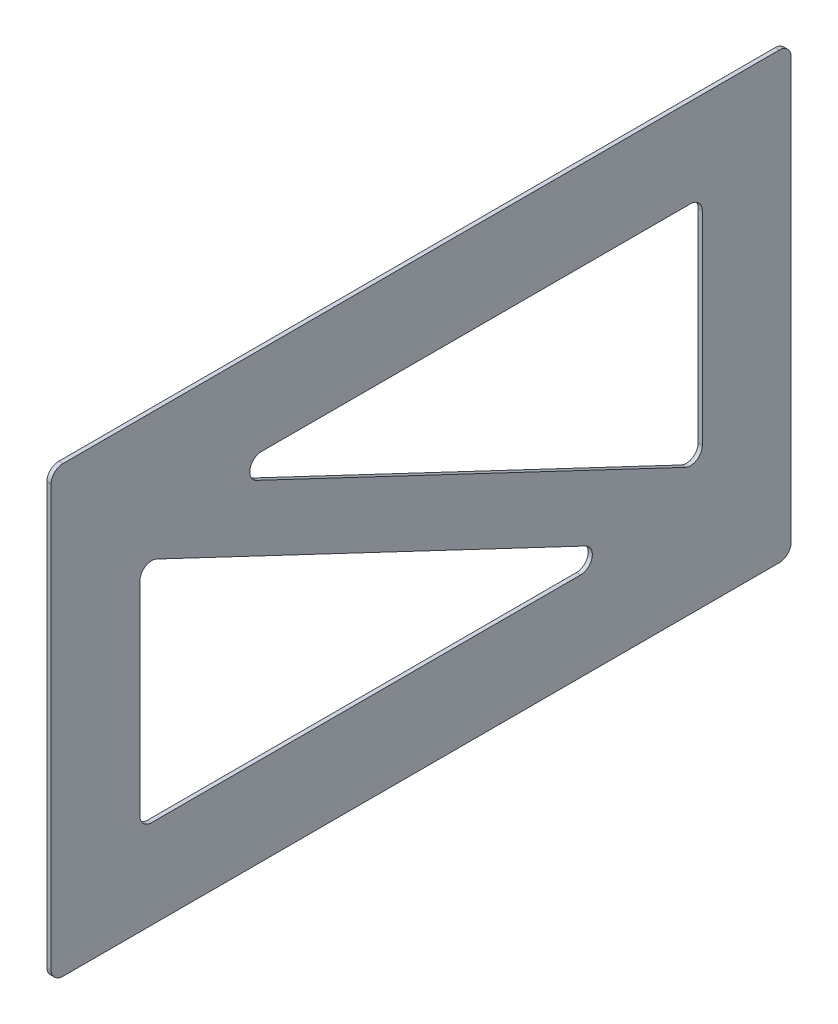
SolidWorks part; units mm, degrees
ref_plane "Front Plane" through (0, 0, 0) normal (0, 0, 1) x (1, 0, 0)
ref_plane "Top Plane" through (0, 0, 0) normal (0, 1, 0) x (1, 0, 0)
ref_plane "Right Plane" through (0, 0, 0) normal (1, 0, 0) x (0, 0, -1)
sketch "Sketch1" plane through (0, 0, 0) normal (1, 0, 0) x (0, 0, -1)
  line L1 (-62.5, 37.5) -> (62.5, 37.5)
  line L2 (-62.5, 37.5) -> (-62.5, -37.5)
  line L3 (-62.5, -37.5) -> (62.5, -37.5)
  line L4 (62.5, 37.5) -> (62.5, -37.5)
  line L5 (-62.5, 37.5) -> (62.5, -37.5) construction
  line L6 (-62.5, -37.5) -> (62.5, 37.5) construction
  point P0 (0, 0)
  dimension "D1" = 125
  dimension "D2" = 75
sheet metal parameters "Sheet-Metal1" thickness 0.7 parameters "D1"=0.7366
base flange "Base-Flange1" sketch "Sketch1" thickness 0.7 reverse thickness direction no parameters "D1"=0.7366
sketch "Sketch10" plane through (0, 0, 0) normal (1, 0, 0) x (0, 0, -1)
  line L0 (-47.5, 22.5) -> (-47.5, -22.5)
  line L1 (-47.5, -22.5) -> (47.5, -22.5)
  line L2 (47.5, -22.5) -> (47.5, 22.5)
  line L3 (47.5, 22.5) -> (-47.5, 22.5)
  line L4 (62.5, 37.5) -> (-62.5, 37.5) construction
  line L5 (-62.5, -37.5) -> (62.5, -37.5) construction
  line L6 (-62.5, 37.5) -> (-62.5, -37.5) construction
  line L7 (62.5, -37.5) -> (62.5, 37.5) construction
  line L8 (-47.5, 22.5) -> (47.5, -22.5) construction
  line L9 (-47.5, 16.9674) -> (35.8201, -22.5)
  line L10 (-35.8201, 22.5) -> (47.5, -16.9674)
  dimension "D1" = 15
  dimension "D2" = 15
  dimension "D3" = 15
  dimension "D4" = 15
  dimension "D5" = 5
  dimension "D6" = 5
extrude "Cut-Extrude1" cut sketch "Sketch10" against normal blind 10 contours L9 L0 L1 | L3 L10 L2 region at (0, -9.3442, 19.7266) region at (0, 9.3442, -19.7266) normal cut yes
fillet "Fillet1" radius 2 10 edges at (-0.35, -37.5, -62.5) (-0.35, -37.5, 62.5) (-0.35, 37.5, -62.5) (-0.35, 37.5, 62.5) (-0.35, -22.5, 47.5) (-0.35, 22.5, 35.8201) (-0.35, 16.9674, 47.5) (-0.35, -22.5, -35.8201) (-0.35, -16.9674, -47.5) (-0.35, 22.5, -47.5)
flat pattern "Flat-Pattern1" [suppressed]
sketch "Bend-Lines1" plane through (0, 0, 0) normal (0, 1, 0) x (1, 0, 0)
sketch3d "Bounding-Box1" [suppressed]
  line L0 (62.5, -37.5, 0) -> (-62.5, -37.5, 0) construction
  line L1 (62.5, 37.5, 0) -> (-62.5, 37.5, 0) construction
  line L2 (62.5, -37.5, 0) -> (62.5, 37.5, 0) construction
  line L3 (-62.5, -37.5, 0) -> (-62.5, 37.5, 0) construction
